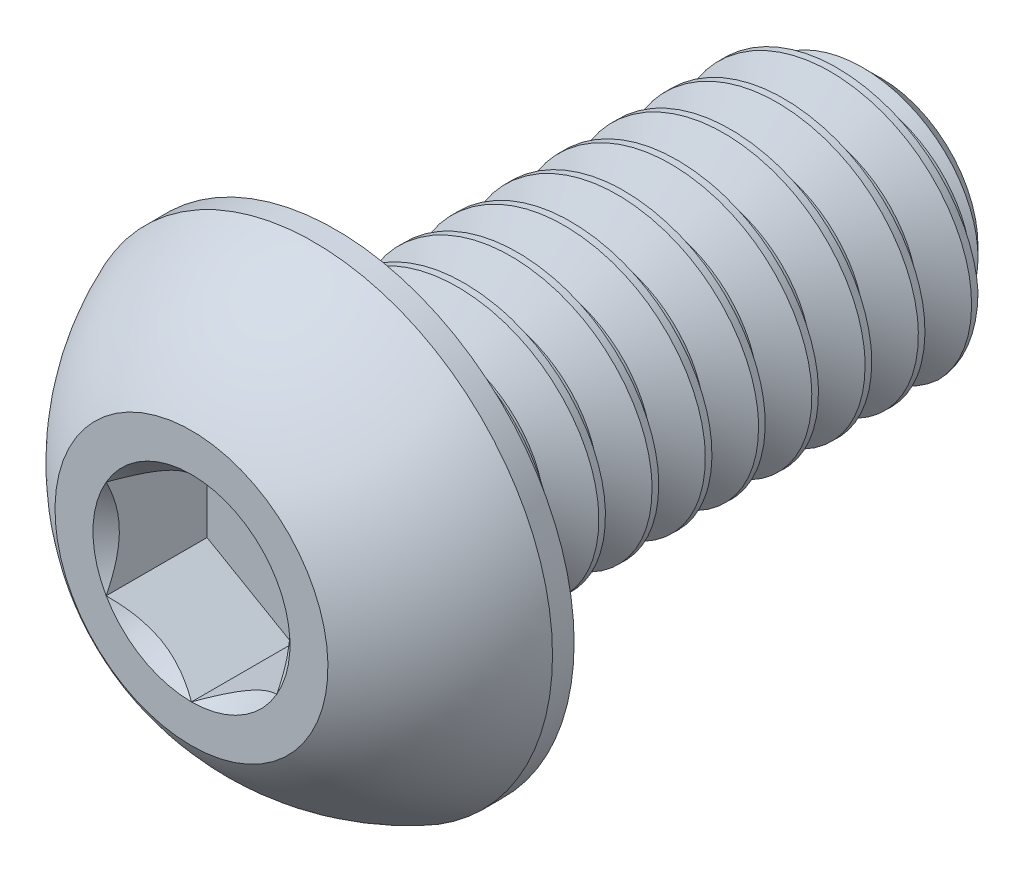
SolidWorks part; units mm, degrees
ref_plane "Front" through (0, 0, 0) normal (0, 0, 1) x (1, 0, 0)
ref_plane "Top" through (0, 0, 0) normal (0, 1, 0) x (1, 0, 0)
ref_plane "Right" through (0, 0, 0) normal (1, 0, 0) x (0, 0, -1)
sketch "Sketch1" plane through (0, 0, 0) normal (1, 0, 0) x (0, 0, -1)
  line L2 (3.3528, 3.175) -> (16.0528, 3.175)
  line L3 (16.0528, 3.175) -> (16.0528, 0)
  line L4 (16.0528, 0) -> (3.3528, 0)
  line L6 (2.8499, 5.5499) -> (3.3528, 5.5499) construction
  line L7 (16.0528, 3.175) -> (16.0528, -3.175) construction
  line L8 (0, 0) -> (3.3528, 0) construction
  line L9 (3.3528, 5.5499) -> (3.3528, -5.5499) construction
  line L11 (3.3528, 3.175) -> (3.3528, 0)
  line L13 (0, 1.9844) -> (0, -1.9844) construction
  line L14 (0, 1.9844) -> (0, 3.175) construction
  arc A3 (0, 3.175) -> (2.8499, 5.5499) centre (5.0603, 0) cw construction
  dimension "D1" = 0.5029
revolve "Revolve1" add sketch "Sketch1" angle 360 mid plane about L4
sketch "Sketch3" plane through (0, 0, -16.0528) normal (0, 0, -1) x (-1, 0, 0)
  circle A0 centre (0, 0) radius 3.175
curve "Helix/Spiral1" pitch 1.239 height 16.0528 radius 3.175 centre (0, 0, -16.0528) axis (0, 0, 1) start towards (0, 1, 0)
sketch "Sketch2" plane through (0, 0, 0) normal (1, 0, 0) x (0, 0, -1)
  line L0 (16.0528, 3.175) -> (17.1369, 3.175)
  line L1 (17.1369, 3.175) -> (16.6723, 2.3702)
  line L2 (16.6723, 2.3702) -> (16.5174, 2.3702)
  line L3 (16.5174, 2.3702) -> (16.0528, 3.175)
  line L4 (16.2851, 2.7726) -> (16.9046, 2.7726) construction
  dimension "D1" = 60
  dimension "D2" = 0.1549
  dimension "D3" = 0.6195
chamfer "Chamfer1" distance 0.9293 angle 45 1 edges at (0, 3.175, -16.0528)
sweep "Cut-Sweep1" cut profiles "Sketch2" path "Helix/Spiral1" align with end faces yes
sketch "Sketch7" plane through (0, 0, 0) normal (1, 0, 0) x (0, 0, -1)
  line L6 (2.8499, 5.5499) -> (3.3528, 5.5499) construction
  line L8 (0, 0) -> (3.3528, 0) construction
  line L11 (3.3528, 5.5499) -> (3.3528, -5.5499) construction
  line L12 (2.8499, 5.5499) -> (3.3528, 5.5499)
  line L13 (0, 0) -> (3.3528, 0)
  line L14 (0, 1.9844) -> (0, -1.9844) construction
  line L15 (3.3528, 5.5499) -> (3.3528, 0)
  line L16 (0, 3.175) -> (0, 0)
  arc A2 (2.8499, 5.5499) -> (0, 3.175) centre (5.0603, 0) ccw construction
  arc A3 (2.8499, 5.5499) -> (0, 3.175) centre (5.0603, 0) ccw
revolve "Revolve2" add sketch "Sketch7" angle 360 mid plane about L13
sketch "Sketch5" plane through (0, 0, 0) normal (0, 0, 1) x (1, 0, 0)
  line L1 (1.9844, -1.1457) -> (1.9844, 1.1457)
  line L2 (1.9844, 1.1457) -> (0, 2.2914)
  line L3 (0, 2.2914) -> (-1.9844, 1.1457)
  line L4 (-1.9844, 1.1457) -> (-1.9844, -1.1457)
  line L5 (-1.9844, -1.1457) -> (0, -2.2914)
  line L6 (0, -2.2914) -> (1.9844, -1.1457)
  circle A0 centre (0, 0) radius 1.9844 construction
extrude "Cut-Extrude2" cut sketch "Sketch5" against normal blind 2.347
sketch "Sketch6" plane through (0, 0, 0) normal (0, 0, 1) x (1, 0, 0)
  circle A0 centre (0, 0) radius 2.2914
extrude "Cut-Extrude3" cut sketch "Sketch6" against normal blind 2.347 draft 45
sketch "Sketch9" [suppressed] plane through (0, 0, -3.3528) normal (0, 0, 1) x (1, 0, 0)
  circle A2 centre (0, 0) radius 3.175
extrude "Boss-Extrude2" [suppressed] add sketch "Sketch9" against normal offset from surface (76.2 mm away) 22.225 up to face at (0, 2.2457, -16.0528)
sketch "Sketch10" plane through (0, 0, 0) normal (1, 0, 0) x (0, 0, -1)
  line L0 (16.0528, 3.175) -> (16.0528, -3.175) construction
  point P0 (14.1943, -3.175)
  dimension "D1" = 1.8585
equation "\"D3@Helix/Spiral1\" = \"Lg@Sketch1\" + \"Head Ht@Sketch1\""
equation "\"D2@Sketch2\" = \"D4@Helix/Spiral1\" * .125"
equation "\"D3@Sketch2\" = \"D4@Helix/Spiral1\" * .5"
equation "\"D1@Chamfer1\" = \"D4@Helix/Spiral1\" * .75"
equation "\"D1@Cut-Extrude2\" = \"Head Ht@Sketch1\" * .7"
equation "\"D1@Sketch1\" = \"Head Ht@Sketch1\" * .15"
equation "\"D1@Sketch10\" = \"D4@Helix/Spiral1\" * 1.5"
equation "\"D1@Cut-Extrude3\" = \"D1@Cut-Extrude2\""
